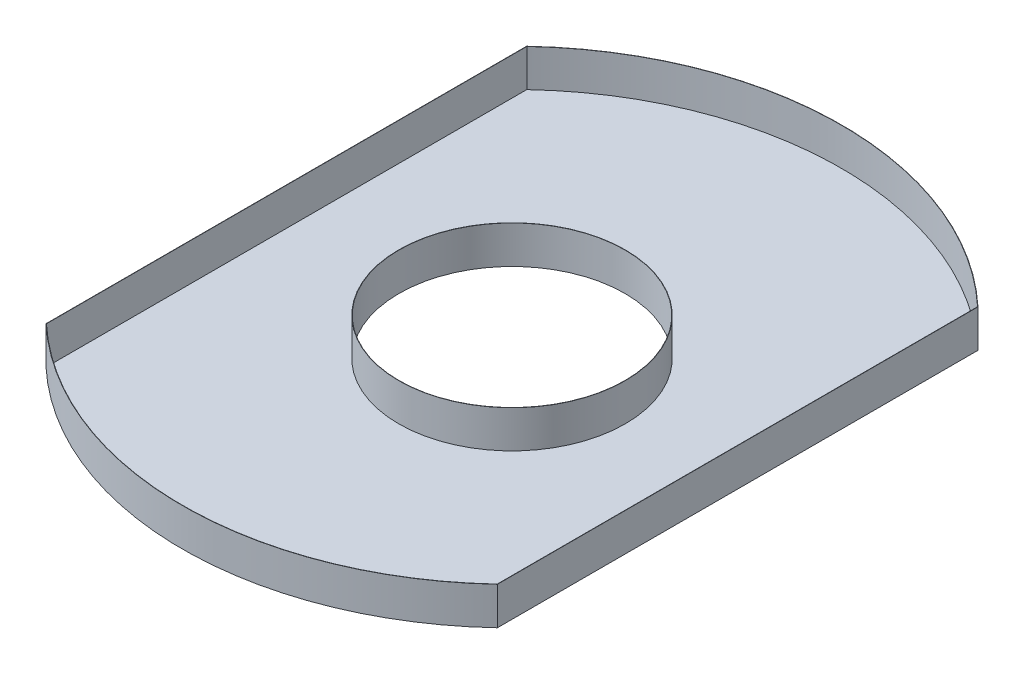
SolidWorks part; units mm, degrees
material "1345 Alloy"
ref_plane "Front Plane" through (0, 0, 0) normal (0, 0, 1) x (1, 0, 0)
ref_plane "Top Plane" through (0, 0, 0) normal (0, 1, 0) x (1, 0, 0)
ref_plane "Right Plane" through (0, 0, 0) normal (1, 0, 0) x (0, 0, -1)
sketch "Sketch1" plane through (0, 0, 0) normal (0, 1, 0) x (1, 0, 0)
  circle A0 centre (0, 0) radius 1750
extrude "Boss-Extrude1" add sketch "Sketch1" along normal blind 500
sketch "Sketch2" plane through (0, 500, 0) normal (0, 1, 0) x (1, 0, 0)
  circle A0 centre (0, 0) radius 900
extrude "Cut-Extrude2" cut sketch "Sketch2" against normal blind 300
sketch "Sketch10" plane through (0, 500, 0) normal (0, 1, 0) x (1, 0, 0)
  line L1 (-2200.588, -2811.5432) -> (2200.588, -2811.5432)
  line L2 (-2200.588, -2811.5432) -> (-2200.588, 2811.5432)
  line L3 (-2200.588, 2811.5432) -> (2200.588, 2811.5432)
  line L4 (2200.588, -2811.5432) -> (2200.588, 2811.5432)
  line L5 (-2200.588, -2811.5432) -> (2200.588, 2811.5432) construction
  line L6 (-2200.588, 2811.5432) -> (2200.588, -2811.5432) construction
  line L7 (-1198.0599, -2169.9586) -> (1198.0599, -2169.9586)
  line L8 (-1198.0599, -2169.9586) -> (-1198.0599, 2169.9586)
  line L9 (-1198.0599, 2169.9586) -> (1198.0599, 2169.9586)
  line L10 (1198.0599, -2169.9586) -> (1198.0599, 2169.9586)
  line L11 (-1198.0599, -2169.9586) -> (1198.0599, 2169.9586) construction
  line L12 (-1198.0599, 2169.9586) -> (1198.0599, -2169.9586) construction
  point P0 (0, 0)
  point P6 (0, 0)
extrude "Cut-Extrude10" cut sketch "Sketch10" against normal through all both and the other way through all
sketch "Sketch3" plane through (0, 0, 0) normal (0, -1, 0) x (1, 0, 0)
  circle A0 centre (0, 0) radius 600
extrude "Cut-Extrude3" cut sketch "Sketch3" against normal blind 300
shell "Shell1" thickness 1.5 removed face at (0, 500, 900)
sketch "Sketch11" plane through (0, 200, 0) normal (0, 1, 0) x (1, 0, 0)
  line L1 (-1546.6788, 2430.4952) -> (1546.6788, 2430.4952)
  line L2 (-1546.6788, 2430.4952) -> (-1546.6788, -2430.4952)
  line L3 (-1546.6788, -2430.4952) -> (1546.6788, -2430.4952)
  line L4 (1546.6788, 2430.4952) -> (1546.6788, -2430.4952)
  line L5 (-1546.6788, 2430.4952) -> (1546.6788, -2430.4952) construction
  line L6 (-1546.6788, -2430.4952) -> (1546.6788, 2430.4952) construction
  point P0 (0, 0)
extrude "Cut-Extrude11" cut sketch "Sketch11" along normal through all
ref_plane "Plane1" through (0, 0, 2000) normal (0, 0, 1) x (1, 0, 0)
sketch "Sketch7" plane through (0, 0, 2000) normal (0, 0, 1) x (1, 0, 0)
  circle A0 centre (0, 133.8976) radius 8.382
extrude "Cut-Extrude6" [suppressed] cut sketch "Sketch7" against normal blind 900
pattern_circular "CirPattern1" [suppressed] count 4 over 360 reverse direction yes of bodies 107
ref_plane "Plane2" through (-1237.4369, 0, 1237.4369) normal (-0.7071, 0, 0.7071) x (0, -1, 0)
sketch "Sketch12" plane through (-1198.0599, 0, 0) normal (-1, 0, 0) x (0, 0, 1)
  line L0 (-828.0253, 88.1097) -> (-805.4725, 65.5569)
  line L1 (-805.4725, 65.5569) -> (-773.578, 65.5569)
  line L2 (-773.578, 65.5569) -> (-751.0253, 88.1097)
  line L3 (-751.0253, 88.1097) -> (-751.0253, 120.0042)
  line L4 (-751.0253, 120.0042) -> (-773.578, 142.5569)
  line L5 (-773.578, 142.5569) -> (-805.4725, 142.5569)
  line L6 (-805.4725, 142.5569) -> (-828.0253, 120.0042)
  line L7 (-828.0253, 120.0042) -> (-828.0253, 88.1097)
  circle A0 centre (-789.5253, 104.0569) radius 38.5 construction
extrude "Cut-Extrude13" [suppressed] cut sketch "Sketch12" against normal blind 10
sketch "Sketch13" plane through (0, 200, 0) normal (0, 1, 0) x (1, 0, 0)
  circle A0 centre (0, 0) radius 901.5 construction
  circle A1 centre (0, 0) radius 901.5
  circle A2 centre (0, 0) radius 601.5
extrude "Cut-Extrude14" cut sketch "Sketch13" against normal blind 10
